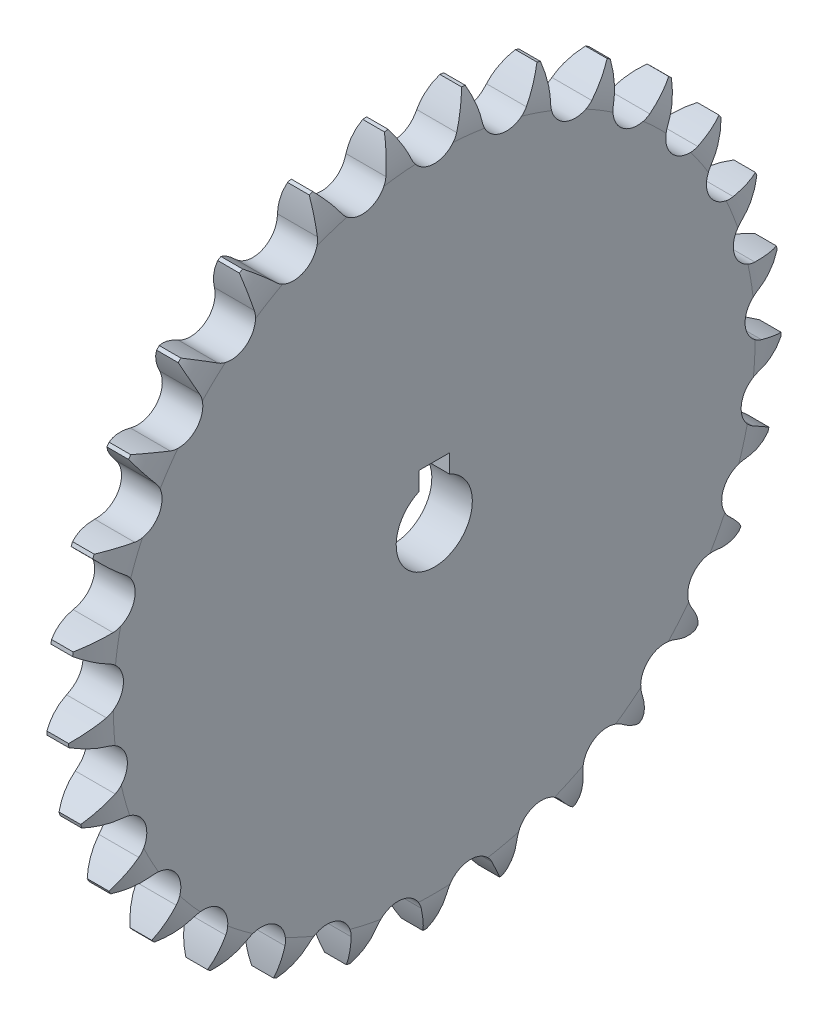
SolidWorks part; units mm, degrees
ref_plane "Plane1" through (0, 0, 0) normal (0, 0, 1) x (1, 0, 0)
ref_plane "Plane2" through (0, 0, 0) normal (0, 1, 0) x (1, 0, 0)
ref_plane "Plane3" through (0, 0, 0) normal (1, 0, 0) x (0, 0, -1)
sketch "Clipboard" plane through (0, 0, 0) normal (0, 1, 0) x (1, 0, 0)
  line L0 (0, 0) -> (8.3308, -4.6178)
  line L1 (-15, 0) -> (100, 0) construction
  line L2 (0, 0) -> (-0.8203, 0.9272)
  line L3 (0, 0) -> (-8.8973, 3.4006)
  line L4 (0, 0) -> (2.7113, 1.5029)
  line L5 (0, 0) -> (-46.8476, -17.4728)
  line L6 (0, 0) -> (-4.4098, -2.9753)
  line L7 (-0.8203, 0.9272) -> (42.4814, 25.9274)
  line L8 (-76.2, 38.1) -> (-73.4, 38.1)
  line L9 (-73.3242, 40.7328) -> (-72.926, 40.7699)
  line L10 (-73.4529, 9.1872) -> (-63.2129, 9.1872)
  circle A0 centre (0, 0) radius 3.175
  circle A1 centre (0, 0) radius 37.5
  circle A2 centre (0, 0) radius 37.5
  dimension "Dr" = 6.35
  dimension "MHD" = 75
  dimension "Hub_dia" = 75
  dimension "Num_teeth" = 29
  dimension "Pitch" = 9.525
  dimension "Width" = 3.1
  dimension "Side_relief" = 1.238
  dimension "Side_radius" = 9.525
  dimension "Overall_len" = 50
  dimension "Show_teeth" = 29
  dimension "Thickness" = 5.3196
  dimension "OAL" = 50.0005
  dimension "T_dim" = 2.8
  dimension "Fillet_rad" = 0.4
  dimension "Face_width" = 5.32
  dimension "Num_strands" = 1
  dimension "Transv_pitch" = 10.24
  dimension "Plate_wid" = 8.26
sketch "BasProSke" plane through (0, 0, 0) normal (0, 1, 0) x (1, 0, 0)
  line L0 (-10, 0) -> (60, 0) construction
  line L1 (0, 0) -> (0, 42.1309)
  line L2 (0, 0) -> (5.3196, 0)
  line L3 (5.3196, 0) -> (5.3196, 42.1309)
  line L4 (4.0816, 46.8268) -> (1.238, 46.8268)
  arc A0 (0, 42.1309) -> (1.238, 46.8268) centre (9.525, 42.1309) cw
  arc A1 (5.3196, 42.1309) -> (4.0816, 46.8268) centre (-4.2054, 42.1309) ccw
  dimension "Thickness" = 5.3196
  dimension "D1" = 9.525
  dimension "G1" = 1.238
  dimension "G2" = 1.238
  dimension "Diameter" = 93.6536
revolve "Base-Revolve" add sketch "BasProSke" angle 360 about L0
sketch "TooCutSke" plane through (0, 0, 0) normal (1, 0, 0) x (0, 0, -1)
  line L0 (0, 44.0804) -> (2.9826, 42.9025) construction
  line L1 (0, 0) -> (0, 107) construction
  line L2 (0, 44.0804) -> (-10, 44.0804) construction
  line L3 (0, 44.0804) -> (-2.9826, 42.9025) construction
  arc A0 (2.9826, 42.9025) -> (5.1154, 47.0495) centre (24.9531, 34.2251) cw
  arc A1 (2.9826, 42.9025) -> (-2.9826, 42.9025) centre (0, 44.0804) cw
  arc A2 (-2.9826, 42.9025) -> (-5.1154, 47.0495) centre (-24.9531, 34.2251) ccw
  arc A3 (5.1154, 47.0495) -> (-5.1154, 47.0495) centre (0, 0) ccw
  dimension "R1" = 3.2067
  dimension "R2" = 23.622
  dimension "Overcut" = 47.3268
  dimension "Seat_radius" = 44.0804
  dimension "X" = 136.897
extrude "ToothCut" cut sketch "TooCutSke" along normal through all
pattern_circular "TeethCuts" count 29 every 12.414 about axis through (-10, 0, 0) along (1, 0, 0) of "ToothCut"
sketch "HubNeaOneSke" plane through (0, 0, 0) normal (-1, 0, 0) x (0, 0, 1)
  circle A0 centre (0, 0) radius 37.5
  dimension "Diameter" = 75
extrude "HubNearOne" [suppressed] add sketch "HubNeaOneSke" along normal blind 44.6809
fillet "HubNearOneFillet" [suppressed] radius 0.4
sketch "HubNeaBotSke" plane through (0, 0, 0) normal (-1, 0, 0) x (0, 0, 1)
  circle A0 centre (0, 0) radius 37.5
  dimension "Diameter" = 75
extrude "HubNearBoth" [suppressed] add sketch "HubNeaBotSke" along normal blind 22.3405
fillet "HubNearBothFillet" [suppressed] radius 0.4
ref_plane "FarPln" through (5.3196, 0, 0) normal (1, 0, 0) x (0, 0, -1)
sketch "HubFarSke" plane through (5.3196, 0, 0) normal (1, 0, 0) x (0, 0, -1)
  circle A0 centre (0, 0) radius 37.5
  dimension "Diameter" = 75
extrude "HubFar" [suppressed] add sketch "HubFarSke" along normal blind 22.3405
fillet "HubFarFillet" [suppressed] radius 0.4
sketch "BorSke" plane through (0, 0, 0) normal (1, 0, 0) x (0, 0, -1)
  circle A0 centre (0, 0) radius 10
  dimension "Diameter" = 20
extrude "Bore" cut sketch "BorSke" along normal mid plane 100.001
sketch "KeySke" plane through (0, 0, 0) normal (1, 0, 0) x (0, 0, -1)
  line L0 (-3, 0) -> (-3, 12.8)
  line L1 (-3, 12.8) -> (3, 12.8)
  line L2 (3, 12.8) -> (3, 0)
  line L3 (0, 0) -> (0, 34) construction
  line L4 (-3, 0) -> (3, 0)
  dimension "Offset" = 12.8
  dimension "Width" = 6
extrude "Keyway" [suppressed] cut sketch "KeySke" along normal mid plane 100.001
pattern_circular "Keyway2" [suppressed] count 2 every 90 about axis through (-10, 0, 0) along (1, 0, 0)
sketch "Sketch1" plane through (5.3196, 0, 0) normal (1, 0, 0) x (0, 0, -1)
  circle A0 centre (0, 0) radius 30
  circle A1 centre (0, 0) radius 5
  dimension "D1" = 60
  dimension "D2" = 10
extrude "Boss-Extrude1" add sketch "Sketch1" along normal offset from surface (24.6804 mm away) 30 up to face at (0, 0, -10)
sketch "Sketch2" plane through (5.3196, 0, 0) normal (-1, 0, 0) x (0, 0, 1)
  circle A0 centre (0, 0) radius 5 construction
  circle A1 centre (0, 0) radius 10
  circle A2 centre (0, 0) radius 10
  circle A3 centre (0, 0) radius 5
  dimension "D1" = 0
extrude "Boss-Extrude2" add sketch "Sketch2" along normal up to surface (5.3196 mm away) up to face at (0, 0, -10)
sketch "Sketch3" plane through (30, 0, 0) normal (1, 0, 0) x (0, 0, -1)
  line L0 (0, 0) -> (0, 5) construction
  line L1 (-2, 7) -> (2, 7)
  line L2 (-2, 7) -> (-2, 3)
  line L3 (-2, 3) -> (2, 3)
  line L4 (2, 7) -> (2, 3)
  line L5 (-2, 7) -> (2, 3) construction
  line L6 (-2, 3) -> (2, 7) construction
  circle A0 centre (0, 0) radius 5 construction
  point P0 (0, 5)
  dimension "D1" = 4
extrude "Cut-Extrude1" cut sketch "Sketch3" against normal through all
sketch "Sketch5" plane through (30, 0, 0) normal (1, 0, 0) x (0, 0, -1)
  circle A0 centre (0, 0) radius 9
  dimension "D1" = 18
extrude "Cut-Extrude3" cut sketch "Sketch5" against normal up to surface (24.6804 mm away) flip side to cut up to face at (5.3196, 0, 30)
sketch "Sketch6" plane through (30, 0, 0) normal (1, 0, 0) x (0, 0, -1)
  circle A0 centre (0, 0) radius 12.5215
extrude "Cut-Extrude4" cut sketch "Sketch6" against normal up to surface (24.6804 mm away)
equation "' \"Pitch@Clipboard\" = 12.7"
equation "' \"Num_strands@Clipboard\" = 1"
equation "' \"Num_teeth@Clipboard\" = 9"
equation "' \"Hub_dia@Clipboard\" = 50"
equation "' \"Overall_len@Clipboard\" = 3"
equation "' \"Diameter@BorSke\" = 12"
equation "' \"T_dim@Clipboard\" = 1"
equation "' \"Width@KeySke\" = 2"
equation "' \"Dr@Clipboard\" = 8.51"
equation "' \"Face_width@Clipboard\" = 7.2"
equation "' \"Side_radius@Clipboard\" = 12.7"
equation "' \"Side_relief@Clipboard\" = 1.27"
equation "' \"Transv_pitch@Clipboard\" = 13.92"
equation "' \"Show_teeth@Clipboard\" = 9"
equation "' \"Fillet_rad@Clipboard\" = 0.6"
equation "' \"Plate_wid@Clipboard\" = 11.8"
equation "\"Num_teeth@Clipboard\" = int( \"Num_teeth@Clipboard\" )"
equation "\"Num_teeth@Clipboard\" = ((sgn( \"Num_teeth@Clipboard\" - 5.0)+1)*( \"Num_teeth@Clipboard\" - 5.0))/2 +5.0"
equation "\"Num_teeth@Clipboard\" = ((sgn( \"Num_teeth@Clipboard\" - 200.0)-1)*( \"Num_teeth@Clipboard\" - 200.0))/-2 +200.0"
equation "\"MHD@Clipboard\" = \"Pitch@Clipboard\" * (1.0 / tan(3.14159265 / \"Num_teeth@Clipboard\" )) - 1.04 * \"Plate_wid@Clipboard\" - 0.76"
equation "\"Thickness@Clipboard\"  = \"Face_width@Clipboard\" + (\"Num_strands@Clipboard\" - 1) * \"Transv_pitch@Clipboard\""
equation "\"OAL@Clipboard\" = \"Thickness@Clipboard\" + 2 * \"Fillet_rad@Clipboard\" + 1"
equation "\"MHD@Clipboard\" = ((sgn( \"MHD@Clipboard\" - \"Hub_dia@Clipboard\" )-1)*( \"MHD@Clipboard\" - \"Hub_dia@Clipboard\" ))/-2+ \"Hub_dia@Clipboard\""
equation "\"OAL@Clipboard\" = ((sgn( \"OAL@Clipboard\" - \"Overall_len@Clipboard\" )+1)*( \"OAL@Clipboard\" - \"Overall_len@Clipboard\" ))/2 + \"Overall_len@Clipboard\" + 0.0005"
equation "\"Num_teeth@TeethCuts\" = int( \"Show_teeth@Clipboard\" ) + 1"
equation "\"Num_teeth@TeethCuts\" = ((sgn( \"Num_teeth@TeethCuts\" - \"Num_teeth@Clipboard\" )-1)*( \"Num_teeth@TeethCuts\" - \"Num_teeth@Clipboard\" ))/-2+ \"Num_teeth@Clipboard\""
equation "\"Num_teeth@TeethCuts\" = ((sgn( \"Num_teeth@TeethCuts\" - 2.0)+1)*( \"Num_teeth@TeethCuts\" - 2.0))/2 +2.0"
equation "\"Angle@TeethCuts\" = 360.0 / \"Num_teeth@Clipboard\""
equation "\"Seat_radius@TooCutSke\" = ( \"Pitch@Clipboard\" / 2.0) / sin(3.14159265 / \"Num_teeth@Clipboard\" ) - \"Dr@Clipboard\" / 2.0 + \"Dr@Clipboard\" * 0.505"
equation "\"R1@TooCutSke\"  = \"Dr@Clipboard\" * 0.505"
equation "\"X@TooCutSke\" = 140.0 - (90.0 / \"Num_teeth@Clipboard\")"
equation "\"R2@TooCutSke\" = 0.12 * \"Dr@Clipboard\" * ( \"Num_teeth@Clipboard\" + 2.0)"
equation "\"Overcut@TooCutSke\" = 0.5 + 0.625 * \"Pitch@Clipboard\" - 0.5 * \"Dr@Clipboard\"  +  \"Pitch@Clipboard\" / 2.0 / sin(3.14159265 / \"Num_teeth@Clipboard\" )"
equation "\"Diameter@BasProSke\" = 2.0 * ( 0.625 * \"Pitch@Clipboard\" - 0.5 * \"Dr@Clipboard\"  +  \"Pitch@Clipboard\" / 2.0 / sin(3.14159265 / \"Num_teeth@Clipboard\" ))"
equation "\"Thickness@BasProSke\"  = \"Thickness@Clipboard\""
equation "\"G1@BasProSke\" =  \"Side_relief@Clipboard\""
equation "\"G2@BasProSke\" =  \"Side_relief@Clipboard\""
equation "\"D1@BasProSke\" =  \"Side_radius@Clipboard\""
equation "\"Diameter@HubNeaOneSke\" = \"MHD@Clipboard\""
equation "\"Length@HubNearOne\" = \"OAL@Clipboard\" - \"Thickness@BasProSke\""
equation "\"Diameter@HubNeaBotSke\" = \"MHD@Clipboard\""
equation "\"Length@HubNearBoth\" = ( \"OAL@Clipboard\" - \"Thickness@BasProSke\" ) / 2.0"
equation "\"D1@HubNearOneFillet\" = \"Fillet_rad@Clipboard\""
equation "\"D1@HubNearBothFillet\" = \"Fillet_rad@Clipboard\""
equation "\"Thickness@FarPln\" = \"Thickness@BasProSke\""
equation "\"Diameter@HubFarSke\" = \"MHD@Clipboard\""
equation "\"Length@HubFar\" = ( \"OAL@Clipboard\" - \"Thickness@BasProSke\" ) / 2.0"
equation "\"D1@HubFarFillet\" = \"Fillet_rad@Clipboard\""
equation "\"D1@Bore\" = \"OAL@Clipboard\" * 2.0"
equation "\"D1@Keyway\" = \"OAL@Clipboard\" * 2.0"
equation "\"Offset@KeySke\" = \"T_dim@Clipboard\" + \"Diameter@BorSke\" / 2.0"
